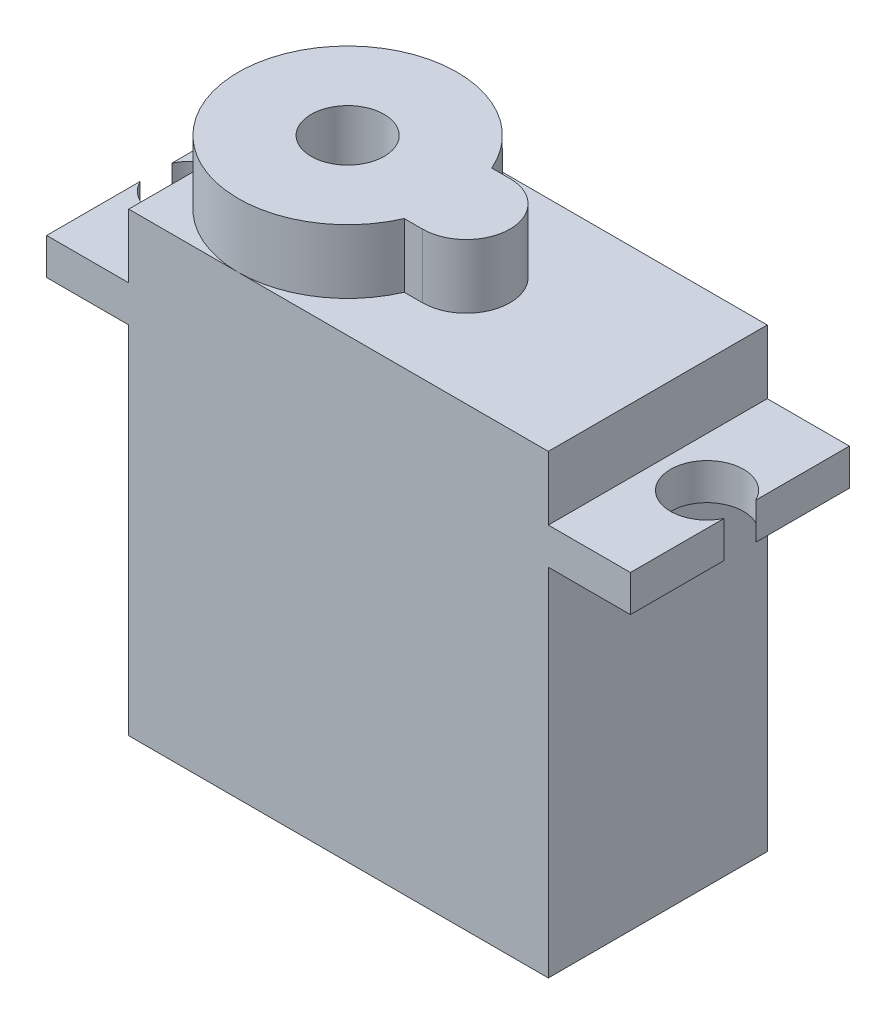
SolidWorks part; units mm, degrees
material "Nylon 101"
ref_plane "Front Plane" through (0, 0, 0) normal (0, 0, 1) x (1, 0, 0)
ref_plane "Top Plane" through (0, 0, 0) normal (0, 1, 0) x (1, 0, 0)
ref_plane "Right Plane" through (0, 0, 0) normal (1, 0, 0) x (0, 0, -1)
sketch "Sketch1" plane through (0, 0, 0) normal (0, 1, 0) x (1, 0, 0)
  line L0 (0, 2.3979) -> (1, 2.3979)
  line L1 (-16, -6) -> (16, -6)
  line L2 (-16, -6) -> (-16, 6)
  line L3 (-16, 6) -> (16, 6)
  line L4 (16, -6) -> (16, 6)
  line L5 (0, 6) -> (0, -6) construction
  line L6 (-16, 0) -> (16, 0) construction
  line L7 (-11.5, -6) -> (11.5, -6)
  line L8 (-11.5, -6) -> (-11.5, 6)
  line L9 (-11.5, 6) -> (11.5, 6)
  line L10 (11.5, -6) -> (11.5, 6)
  line L11 (0, 6) -> (0, -6) construction
  line L12 (-11.5, 0) -> (11.5, 0) construction
  line L14 (0, -2.3979) -> (1, -2.3979)
  circle A0 centre (-5.5, 0) radius 6
  arc A1 (1, -2.3979) -> (1, 2.3979) centre (1, 0) ccw
  circle A3 centre (-14.2, 0) radius 2
  circle A4 centre (14.2, 0) radius 2
  circle A5 centre (-5.5, 0) radius 2
  point P0 (0, 0)
  point P4 (0, 0)
  dimension "D4" = 1
  dimension "D6" = 4
  dimension "D8" = 4
  dimension "D1" = 12
  dimension "D2" = 32
  dimension "D3" = 23
  dimension "D5" = 1
  dimension "D7" = 1.8
extrude "Boss-Extrude1" add sketch "Sketch1" along normal blind 25 contours A0 A5 | A1 L14 A0 L7 L10 L9 L0 | A0 L8 L1 | L14 A1 L0 A0 | A0 L3 L8 region at (5.6103, 0, 0) region at (1.6617, 0, 0) region at (0.2075, 0, -1.1901) region at (-10.1598, 0, -4.6598) region at (-10.1598, 0, 4.6598)
extrude "Boss-Extrude2" add sketch "Sketch1<4>" along normal blind 2 from offset 19.5 contours L4 A4 L3 L10 L1 | A3 L2 L1 L8 L3 region at (-11.6282, 0, -3) region at (13.75, 0, -5.8718)
sketch "Sketch1<4>" plane through (0, 0, 0) normal (0, 1, 0) x (1, 0, 0) same geometry as "Sketch1"
extrude "Boss-Extrude3" add sketch "Sketch1<6>" along normal blind 3.5 from surface contours A0 A5 | L14 A1 L0 A0 region at (1.6617, 0, 0) region at (0.2075, 0, -1.1901) starting at face at (-5.5, 25, 2)
sketch "Sketch1<6>" plane through (0, 0, 0) normal (0, 1, 0) x (1, 0, 0) same geometry as "Sketch1"
extrude "Boss-Extrude4" add sketch "Sketch1<7>" along normal blind 5 contours A5
sketch "Sketch1<7>" plane through (0, 0, 0) normal (0, 1, 0) x (1, 0, 0) same geometry as "Sketch1"
